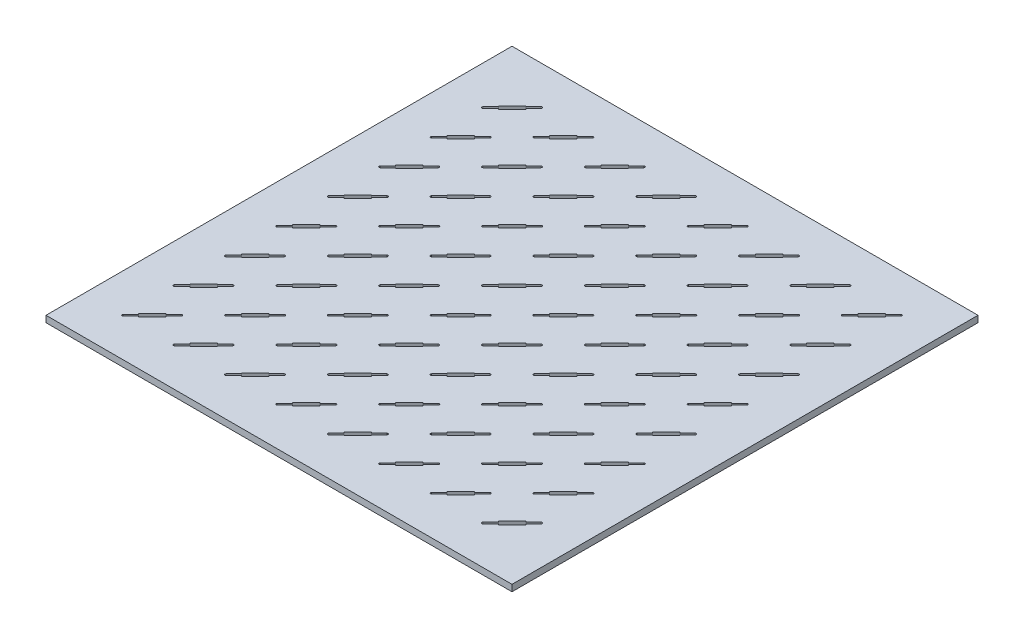
SolidWorks part; units mm, degrees
material "Acrylic (Medium-high impact)"
ref_plane "Front Plane" through (0, 0, 0) normal (0, 0, 1) x (1, 0, 0)
ref_plane "Top Plane" through (0, 0, 0) normal (0, 1, 0) x (1, 0, 0)
ref_plane "Right Plane" through (0, 0, 0) normal (1, 0, 0) x (0, 0, -1)
sketch "Sketch1" plane through (0, 0, 0) normal (0, 1, 0) x (1, 0, 0)
  line L1 (0, 0) -> (431.8, 0)
  line L2 (0, 0) -> (0, 431.8)
  line L3 (0, 431.8) -> (431.8, 431.8)
  line L4 (431.8, 0) -> (431.8, 431.8)
  dimension "D1" = 431.8
  dimension "D2" = 431.8
extrude "Boss-Extrude1" add sketch "Sketch1" along normal blind 6
sketch "Sketch2" plane through (0, 6, 0) normal (0, 1, 0) x (1, 0, 0)
  line L0 (73.025, 25.4) -> (73.025, 73.025) construction
  line L1 (25.4, 25.4) -> (73.025, 25.4) construction
  line L2 (25.4, 25.4) -> (25.4, 73.025) construction
  line L3 (25.4, 73.025) -> (73.025, 73.025) construction
  line L4 (73.025, 25.4) -> (73.025, 73.025) construction
  line L5 (73.025, 25.4) -> (120.65, 25.4) construction
  line L6 (120.65, 25.4) -> (120.65, 73.025) construction
  line L7 (73.025, 73.025) -> (120.65, 73.025) construction
  line L8 (120.65, 25.4) -> (120.65, 73.025) construction
  line L9 (120.65, 25.4) -> (168.275, 25.4) construction
  line L10 (168.275, 25.4) -> (168.275, 73.025) construction
  line L11 (120.65, 73.025) -> (168.275, 73.025) construction
  line L12 (168.275, 25.4) -> (168.275, 73.025) construction
  line L13 (168.275, 25.4) -> (215.9, 25.4) construction
  line L14 (215.9, 25.4) -> (215.9, 73.025) construction
  line L15 (168.275, 73.025) -> (215.9, 73.025) construction
  line L16 (215.9, 25.4) -> (215.9, 73.025) construction
  line L17 (215.9, 25.4) -> (263.525, 25.4) construction
  line L18 (263.525, 25.4) -> (263.525, 73.025) construction
  line L19 (215.9, 73.025) -> (263.525, 73.025) construction
  line L20 (263.525, 25.4) -> (263.525, 73.025) construction
  line L21 (263.525, 25.4) -> (311.15, 25.4) construction
  line L22 (311.15, 25.4) -> (311.15, 73.025) construction
  line L23 (263.525, 73.025) -> (311.15, 73.025) construction
  line L24 (311.15, 25.4) -> (311.15, 73.025) construction
  line L25 (311.15, 25.4) -> (358.775, 25.4) construction
  line L26 (358.775, 25.4) -> (358.775, 73.025) construction
  line L27 (311.15, 73.025) -> (358.775, 73.025) construction
  line L28 (358.775, 25.4) -> (358.775, 73.025) construction
  line L29 (358.775, 25.4) -> (406.4, 25.4) construction
  line L30 (406.4, 25.4) -> (406.4, 73.025) construction
  line L31 (358.775, 73.025) -> (406.4, 73.025) construction
  line L32 (73.025, 73.025) -> (73.025, 120.65) construction
  line L33 (73.025, 73.025) -> (120.65, 73.025) construction
  line L34 (120.65, 73.025) -> (120.65, 120.65) construction
  line L35 (73.025, 120.65) -> (120.65, 120.65) construction
  line L36 (120.65, 73.025) -> (120.65, 120.65) construction
  line L37 (120.65, 73.025) -> (168.275, 73.025) construction
  line L38 (168.275, 73.025) -> (168.275, 120.65) construction
  line L39 (120.65, 120.65) -> (168.275, 120.65) construction
  line L40 (168.275, 73.025) -> (168.275, 120.65) construction
  line L41 (168.275, 73.025) -> (215.9, 73.025) construction
  line L42 (215.9, 73.025) -> (215.9, 120.65) construction
  line L43 (168.275, 120.65) -> (215.9, 120.65) construction
  line L44 (215.9, 73.025) -> (215.9, 120.65) construction
  line L45 (215.9, 73.025) -> (263.525, 73.025) construction
  line L46 (263.525, 73.025) -> (263.525, 120.65) construction
  line L47 (215.9, 120.65) -> (263.525, 120.65) construction
  line L48 (263.525, 73.025) -> (263.525, 120.65) construction
  line L49 (263.525, 73.025) -> (311.15, 73.025) construction
  line L50 (311.15, 73.025) -> (311.15, 120.65) construction
  line L51 (263.525, 120.65) -> (311.15, 120.65) construction
  line L52 (311.15, 73.025) -> (311.15, 120.65) construction
  line L53 (311.15, 73.025) -> (358.775, 73.025) construction
  line L54 (358.775, 73.025) -> (358.775, 120.65) construction
  line L55 (311.15, 120.65) -> (358.775, 120.65) construction
  line L56 (358.775, 73.025) -> (358.775, 120.65) construction
  line L57 (358.775, 73.025) -> (406.4, 73.025) construction
  line L58 (406.4, 73.025) -> (406.4, 120.65) construction
  line L59 (358.775, 120.65) -> (406.4, 120.65) construction
  line L60 (73.025, 120.65) -> (73.025, 168.275) construction
  line L61 (73.025, 120.65) -> (120.65, 120.65) construction
  line L62 (120.65, 120.65) -> (120.65, 168.275) construction
  line L63 (73.025, 168.275) -> (120.65, 168.275) construction
  line L64 (120.65, 120.65) -> (120.65, 168.275) construction
  line L65 (120.65, 120.65) -> (168.275, 120.65) construction
  line L66 (168.275, 120.65) -> (168.275, 168.275) construction
  line L67 (120.65, 168.275) -> (168.275, 168.275) construction
  line L68 (168.275, 120.65) -> (168.275, 168.275) construction
  line L69 (168.275, 120.65) -> (215.9, 120.65) construction
  line L70 (215.9, 120.65) -> (215.9, 168.275) construction
  line L71 (168.275, 168.275) -> (215.9, 168.275) construction
  line L72 (215.9, 120.65) -> (215.9, 168.275) construction
  line L73 (215.9, 120.65) -> (263.525, 120.65) construction
  line L74 (263.525, 120.65) -> (263.525, 168.275) construction
  line L75 (215.9, 168.275) -> (263.525, 168.275) construction
  line L76 (263.525, 120.65) -> (263.525, 168.275) construction
  line L77 (263.525, 120.65) -> (311.15, 120.65) construction
  line L78 (311.15, 120.65) -> (311.15, 168.275) construction
  line L79 (263.525, 168.275) -> (311.15, 168.275) construction
  line L80 (311.15, 120.65) -> (311.15, 168.275) construction
  line L81 (311.15, 120.65) -> (358.775, 120.65) construction
  line L82 (358.775, 120.65) -> (358.775, 168.275) construction
  line L83 (311.15, 168.275) -> (358.775, 168.275) construction
  line L84 (358.775, 120.65) -> (358.775, 168.275) construction
  line L85 (358.775, 120.65) -> (406.4, 120.65) construction
  line L86 (406.4, 120.65) -> (406.4, 168.275) construction
  line L87 (358.775, 168.275) -> (406.4, 168.275) construction
  line L88 (73.025, 168.275) -> (73.025, 215.9) construction
  line L89 (73.025, 168.275) -> (120.65, 168.275) construction
  line L90 (120.65, 168.275) -> (120.65, 215.9) construction
  line L91 (73.025, 215.9) -> (120.65, 215.9) construction
  line L92 (120.65, 168.275) -> (120.65, 215.9) construction
  line L93 (120.65, 168.275) -> (168.275, 168.275) construction
  line L94 (168.275, 168.275) -> (168.275, 215.9) construction
  line L95 (120.65, 215.9) -> (168.275, 215.9) construction
  line L96 (168.275, 168.275) -> (168.275, 215.9) construction
  line L97 (168.275, 168.275) -> (215.9, 168.275) construction
  line L98 (215.9, 168.275) -> (215.9, 215.9) construction
  line L99 (168.275, 215.9) -> (215.9, 215.9) construction
  line L100 (215.9, 168.275) -> (215.9, 215.9) construction
  line L101 (215.9, 168.275) -> (263.525, 168.275) construction
  line L102 (263.525, 168.275) -> (263.525, 215.9) construction
  line L103 (215.9, 215.9) -> (263.525, 215.9) construction
  line L104 (263.525, 168.275) -> (263.525, 215.9) construction
  line L105 (263.525, 168.275) -> (311.15, 168.275) construction
  line L106 (311.15, 168.275) -> (311.15, 215.9) construction
  line L107 (263.525, 215.9) -> (311.15, 215.9) construction
  line L108 (311.15, 168.275) -> (311.15, 215.9) construction
  line L109 (311.15, 168.275) -> (358.775, 168.275) construction
  line L110 (358.775, 168.275) -> (358.775, 215.9) construction
  line L111 (311.15, 215.9) -> (358.775, 215.9) construction
  line L112 (358.775, 168.275) -> (358.775, 215.9) construction
  line L113 (358.775, 168.275) -> (406.4, 168.275) construction
  line L114 (406.4, 168.275) -> (406.4, 215.9) construction
  line L115 (358.775, 215.9) -> (406.4, 215.9) construction
  line L116 (73.025, 215.9) -> (73.025, 263.525) construction
  line L117 (73.025, 215.9) -> (120.65, 215.9) construction
  line L118 (120.65, 215.9) -> (120.65, 263.525) construction
  line L119 (73.025, 263.525) -> (120.65, 263.525) construction
  line L120 (120.65, 215.9) -> (120.65, 263.525) construction
  line L121 (120.65, 215.9) -> (168.275, 215.9) construction
  line L122 (168.275, 215.9) -> (168.275, 263.525) construction
  line L123 (120.65, 263.525) -> (168.275, 263.525) construction
  line L124 (168.275, 215.9) -> (168.275, 263.525) construction
  line L125 (168.275, 215.9) -> (215.9, 215.9) construction
  line L126 (215.9, 215.9) -> (215.9, 263.525) construction
  line L127 (168.275, 263.525) -> (215.9, 263.525) construction
  line L128 (215.9, 215.9) -> (215.9, 263.525) construction
  line L129 (215.9, 215.9) -> (263.525, 215.9) construction
  line L130 (263.525, 215.9) -> (263.525, 263.525) construction
  line L131 (215.9, 263.525) -> (263.525, 263.525) construction
  line L132 (263.525, 215.9) -> (263.525, 263.525) construction
  line L133 (263.525, 215.9) -> (311.15, 215.9) construction
  line L134 (311.15, 215.9) -> (311.15, 263.525) construction
  line L135 (263.525, 263.525) -> (311.15, 263.525) construction
  line L136 (311.15, 215.9) -> (311.15, 263.525) construction
  line L137 (311.15, 215.9) -> (358.775, 215.9) construction
  line L138 (358.775, 215.9) -> (358.775, 263.525) construction
  line L139 (311.15, 263.525) -> (358.775, 263.525) construction
  line L140 (358.775, 215.9) -> (358.775, 263.525) construction
  line L141 (358.775, 215.9) -> (406.4, 215.9) construction
  line L142 (406.4, 215.9) -> (406.4, 263.525) construction
  line L143 (358.775, 263.525) -> (406.4, 263.525) construction
  line L144 (73.025, 263.525) -> (73.025, 311.15) construction
  line L145 (73.025, 263.525) -> (120.65, 263.525) construction
  line L146 (120.65, 263.525) -> (120.65, 311.15) construction
  line L147 (73.025, 311.15) -> (120.65, 311.15) construction
  line L148 (120.65, 263.525) -> (120.65, 311.15) construction
  line L149 (120.65, 263.525) -> (168.275, 263.525) construction
  line L150 (168.275, 263.525) -> (168.275, 311.15) construction
  line L151 (120.65, 311.15) -> (168.275, 311.15) construction
  line L152 (168.275, 263.525) -> (168.275, 311.15) construction
  line L153 (168.275, 263.525) -> (215.9, 263.525) construction
  line L154 (215.9, 263.525) -> (215.9, 311.15) construction
  line L155 (168.275, 311.15) -> (215.9, 311.15) construction
  line L156 (215.9, 263.525) -> (215.9, 311.15) construction
  line L157 (215.9, 263.525) -> (263.525, 263.525) construction
  line L158 (263.525, 263.525) -> (263.525, 311.15) construction
  line L159 (215.9, 311.15) -> (263.525, 311.15) construction
  line L160 (263.525, 263.525) -> (263.525, 311.15) construction
  line L161 (263.525, 263.525) -> (311.15, 263.525) construction
  line L162 (311.15, 263.525) -> (311.15, 311.15) construction
  line L163 (263.525, 311.15) -> (311.15, 311.15) construction
  line L164 (311.15, 263.525) -> (311.15, 311.15) construction
  line L165 (311.15, 263.525) -> (358.775, 263.525) construction
  line L166 (358.775, 263.525) -> (358.775, 311.15) construction
  line L167 (311.15, 311.15) -> (358.775, 311.15) construction
  line L168 (358.775, 263.525) -> (358.775, 311.15) construction
  line L169 (358.775, 263.525) -> (406.4, 263.525) construction
  line L170 (406.4, 263.525) -> (406.4, 311.15) construction
  line L171 (358.775, 311.15) -> (406.4, 311.15) construction
  line L172 (73.025, 311.15) -> (73.025, 358.775) construction
  line L173 (73.025, 311.15) -> (120.65, 311.15) construction
  line L174 (120.65, 311.15) -> (120.65, 358.775) construction
  line L175 (73.025, 358.775) -> (120.65, 358.775) construction
  line L176 (120.65, 311.15) -> (120.65, 358.775) construction
  line L177 (120.65, 311.15) -> (168.275, 311.15) construction
  line L178 (168.275, 311.15) -> (168.275, 358.775) construction
  line L179 (120.65, 358.775) -> (168.275, 358.775) construction
  line L180 (168.275, 311.15) -> (168.275, 358.775) construction
  line L181 (168.275, 311.15) -> (215.9, 311.15) construction
  line L182 (215.9, 311.15) -> (215.9, 358.775) construction
  line L183 (168.275, 358.775) -> (215.9, 358.775) construction
  line L184 (215.9, 311.15) -> (215.9, 358.775) construction
  line L185 (215.9, 311.15) -> (263.525, 311.15) construction
  line L186 (263.525, 311.15) -> (263.525, 358.775) construction
  line L187 (215.9, 358.775) -> (263.525, 358.775) construction
  line L188 (263.525, 311.15) -> (263.525, 358.775) construction
  line L189 (263.525, 311.15) -> (311.15, 311.15) construction
  line L190 (311.15, 311.15) -> (311.15, 358.775) construction
  line L191 (263.525, 358.775) -> (311.15, 358.775) construction
  line L192 (311.15, 311.15) -> (311.15, 358.775) construction
  line L193 (311.15, 311.15) -> (358.775, 311.15) construction
  line L194 (358.775, 311.15) -> (358.775, 358.775) construction
  line L195 (311.15, 358.775) -> (358.775, 358.775) construction
  line L196 (358.775, 311.15) -> (358.775, 358.775) construction
  line L197 (358.775, 311.15) -> (406.4, 311.15) construction
  line L198 (406.4, 311.15) -> (406.4, 358.775) construction
  line L199 (358.775, 358.775) -> (406.4, 358.775) construction
  line L200 (73.025, 358.775) -> (73.025, 406.4) construction
  line L201 (73.025, 358.775) -> (120.65, 358.775) construction
  line L202 (120.65, 358.775) -> (120.65, 406.4) construction
  line L203 (73.025, 406.4) -> (120.65, 406.4) construction
  line L204 (120.65, 358.775) -> (120.65, 406.4) construction
  line L205 (120.65, 358.775) -> (168.275, 358.775) construction
  line L206 (168.275, 358.775) -> (168.275, 406.4) construction
  line L207 (120.65, 406.4) -> (168.275, 406.4) construction
  line L208 (168.275, 358.775) -> (168.275, 406.4) construction
  line L209 (168.275, 358.775) -> (215.9, 358.775) construction
  line L210 (215.9, 358.775) -> (215.9, 406.4) construction
  line L211 (168.275, 406.4) -> (215.9, 406.4) construction
  line L212 (215.9, 358.775) -> (215.9, 406.4) construction
  line L213 (215.9, 358.775) -> (263.525, 358.775) construction
  line L214 (263.525, 358.775) -> (263.525, 406.4) construction
  line L215 (215.9, 406.4) -> (263.525, 406.4) construction
  line L216 (263.525, 358.775) -> (263.525, 406.4) construction
  line L217 (263.525, 358.775) -> (311.15, 358.775) construction
  line L218 (311.15, 358.775) -> (311.15, 406.4) construction
  line L219 (263.525, 406.4) -> (311.15, 406.4) construction
  line L220 (311.15, 358.775) -> (311.15, 406.4) construction
  line L221 (311.15, 358.775) -> (358.775, 358.775) construction
  line L222 (358.775, 358.775) -> (358.775, 406.4) construction
  line L223 (311.15, 406.4) -> (358.775, 406.4) construction
  line L224 (358.775, 358.775) -> (358.775, 406.4) construction
  line L225 (358.775, 358.775) -> (406.4, 358.775) construction
  line L226 (406.4, 358.775) -> (406.4, 406.4) construction
  line L227 (358.775, 406.4) -> (406.4, 406.4) construction
  line L228 (25.4, 73.025) -> (25.4, 120.65) construction
  line L229 (25.4, 73.025) -> (73.025, 73.025) construction
  line L230 (73.025, 73.025) -> (73.025, 120.65) construction
  line L231 (25.4, 120.65) -> (73.025, 120.65) construction
  line L232 (25.4, 120.65) -> (25.4, 168.275) construction
  line L233 (25.4, 120.65) -> (73.025, 120.65) construction
  line L234 (73.025, 120.65) -> (73.025, 168.275) construction
  line L235 (25.4, 168.275) -> (73.025, 168.275) construction
  line L236 (25.4, 168.275) -> (25.4, 215.9) construction
  line L237 (25.4, 168.275) -> (73.025, 168.275) construction
  line L238 (73.025, 168.275) -> (73.025, 215.9) construction
  line L239 (25.4, 215.9) -> (73.025, 215.9) construction
  line L240 (25.4, 215.9) -> (25.4, 263.525) construction
  line L241 (25.4, 215.9) -> (73.025, 215.9) construction
  line L242 (73.025, 215.9) -> (73.025, 263.525) construction
  line L243 (25.4, 263.525) -> (73.025, 263.525) construction
  line L244 (25.4, 263.525) -> (25.4, 311.15) construction
  line L245 (25.4, 263.525) -> (73.025, 263.525) construction
  line L246 (73.025, 263.525) -> (73.025, 311.15) construction
  line L247 (25.4, 311.15) -> (73.025, 311.15) construction
  line L248 (25.4, 311.15) -> (25.4, 358.775) construction
  line L249 (25.4, 311.15) -> (73.025, 311.15) construction
  line L250 (73.025, 311.15) -> (73.025, 358.775) construction
  line L251 (25.4, 358.775) -> (73.025, 358.775) construction
  line L252 (25.4, 358.775) -> (25.4, 406.4) construction
  line L253 (25.4, 358.775) -> (73.025, 358.775) construction
  line L254 (73.025, 358.775) -> (73.025, 406.4) construction
  line L255 (25.4, 406.4) -> (73.025, 406.4) construction
  line L256 (0, 0) -> (431.8, 0) construction
  line L257 (0, 431.8) -> (0, 0) construction
  line L259 (431.8, 431.8) -> (0, 431.8) construction
  line L260 (431.8, 0) -> (431.8, 431.8) construction
  line L261 (73.025, 73.025) -> (25.4, 25.4) construction
  line L266 (42.1408, 43.555) -> (35.0697, 36.4839)
  line L906 (56.99, 54.1616) -> (56.2829, 54.8687)
  line L922 (56.99, 54.1616) -> (44.2621, 41.4336)
  line L923 (44.2621, 41.4336) -> (43.555, 42.1408)
  line L924 (54.1616, 56.99) -> (41.4336, 44.2621)
  line L925 (35.0697, 36.4839) -> (36.4839, 35.0697)
  line L926 (36.4839, 35.0697) -> (43.555, 42.1408)
  line L927 (42.1408, 43.555) -> (41.4336, 44.2621)
  line L928 (54.8687, 56.2829) -> (61.9397, 63.354)
  line L929 (61.9397, 63.354) -> (63.354, 61.9397)
  line L930 (63.354, 61.9397) -> (56.2829, 54.8687)
  line L931 (54.8687, 56.2829) -> (54.1616, 56.99)
  line L932 (25.4, 73.025) -> (73.025, 25.4) construction
  line L933 (56.99, 101.7916) -> (56.2829, 102.4987)
  line L934 (63.354, 109.5697) -> (56.2829, 102.4987)
  line L935 (61.9397, 110.984) -> (63.354, 109.5697)
  line L936 (54.8687, 103.9129) -> (61.9397, 110.984)
  line L937 (54.8687, 103.9129) -> (54.1616, 104.62)
  line L938 (54.1616, 104.62) -> (41.4336, 91.8921)
  line L939 (42.1408, 91.185) -> (41.4336, 91.8921)
  line L940 (42.1408, 91.185) -> (35.0697, 84.1139)
  line L941 (35.0697, 84.1139) -> (36.4839, 82.6997)
  line L942 (36.4839, 82.6997) -> (43.555, 89.7708)
  line L943 (44.2621, 89.0636) -> (43.555, 89.7708)
  line L944 (56.99, 101.7916) -> (44.2621, 89.0636)
  line L945 (56.99, 149.4216) -> (56.2829, 150.1287)
  line L946 (63.354, 157.1997) -> (56.2829, 150.1287)
  line L947 (61.9397, 158.614) -> (63.354, 157.1997)
  line L948 (54.8687, 151.5429) -> (61.9397, 158.614)
  line L949 (54.8687, 151.5429) -> (54.1616, 152.25)
  line L950 (54.1616, 152.25) -> (41.4336, 139.5221)
  line L951 (42.1408, 138.815) -> (41.4336, 139.5221)
  line L952 (42.1408, 138.815) -> (35.0697, 131.7439)
  line L953 (35.0697, 131.7439) -> (36.4839, 130.3297)
  line L954 (36.4839, 130.3297) -> (43.555, 137.4008)
  line L955 (44.2621, 136.6936) -> (43.555, 137.4008)
  line L956 (56.99, 149.4216) -> (44.2621, 136.6936)
  line L957 (56.99, 197.0516) -> (56.2829, 197.7587)
  line L958 (63.354, 204.8297) -> (56.2829, 197.7587)
  line L959 (61.9397, 206.244) -> (63.354, 204.8297)
  line L960 (54.8687, 199.1729) -> (61.9397, 206.244)
  line L961 (54.8687, 199.1729) -> (54.1616, 199.88)
  line L962 (54.1616, 199.88) -> (41.4336, 187.1521)
  line L963 (42.1408, 186.445) -> (41.4336, 187.1521)
  line L964 (42.1408, 186.445) -> (35.0697, 179.3739)
  line L965 (35.0697, 179.3739) -> (36.4839, 177.9597)
  line L966 (36.4839, 177.9597) -> (43.555, 185.0308)
  line L967 (44.2621, 184.3236) -> (43.555, 185.0308)
  line L968 (56.99, 197.0516) -> (44.2621, 184.3236)
  line L969 (56.99, 244.6816) -> (56.2829, 245.3887)
  line L970 (63.354, 252.4597) -> (56.2829, 245.3887)
  line L971 (61.9397, 253.874) -> (63.354, 252.4597)
  line L972 (54.8687, 246.8029) -> (61.9397, 253.874)
  line L973 (54.8687, 246.8029) -> (54.1616, 247.51)
  line L974 (54.1616, 247.51) -> (41.4336, 234.7821)
  line L975 (42.1408, 234.075) -> (41.4336, 234.7821)
  line L976 (42.1408, 234.075) -> (35.0697, 227.0039)
  line L977 (35.0697, 227.0039) -> (36.4839, 225.5897)
  line L978 (36.4839, 225.5897) -> (43.555, 232.6608)
  line L979 (44.2621, 231.9536) -> (43.555, 232.6608)
  line L980 (56.99, 244.6816) -> (44.2621, 231.9536)
  line L981 (56.99, 292.3116) -> (56.2829, 293.0187)
  line L982 (63.354, 300.0897) -> (56.2829, 293.0187)
  line L983 (61.9397, 301.504) -> (63.354, 300.0897)
  line L984 (54.8687, 294.4329) -> (61.9397, 301.504)
  line L985 (54.8687, 294.4329) -> (54.1616, 295.14)
  line L986 (54.1616, 295.14) -> (41.4336, 282.4121)
  line L987 (42.1408, 281.705) -> (41.4336, 282.4121)
  line L988 (42.1408, 281.705) -> (35.0697, 274.6339)
  line L989 (35.0697, 274.6339) -> (36.4839, 273.2197)
  line L990 (36.4839, 273.2197) -> (43.555, 280.2908)
  line L991 (44.2621, 279.5836) -> (43.555, 280.2908)
  line L992 (56.99, 292.3116) -> (44.2621, 279.5836)
  line L993 (56.99, 339.9416) -> (56.2829, 340.6487)
  line L994 (63.354, 347.7197) -> (56.2829, 340.6487)
  line L995 (61.9397, 349.134) -> (63.354, 347.7197)
  line L996 (54.8687, 342.0629) -> (61.9397, 349.134)
  line L997 (54.8687, 342.0629) -> (54.1616, 342.77)
  line L998 (54.1616, 342.77) -> (41.4336, 330.0421)
  line L999 (42.1408, 329.335) -> (41.4336, 330.0421)
  line L1000 (42.1408, 329.335) -> (35.0697, 322.2639)
  line L1001 (35.0697, 322.2639) -> (36.4839, 320.8497)
  line L1002 (36.4839, 320.8497) -> (43.555, 327.9208)
  line L1003 (44.2621, 327.2136) -> (43.555, 327.9208)
  line L1004 (56.99, 339.9416) -> (44.2621, 327.2136)
  line L1005 (56.99, 387.5716) -> (56.2829, 388.2787)
  line L1006 (63.354, 395.3497) -> (56.2829, 388.2787)
  line L1007 (61.9397, 396.764) -> (63.354, 395.3497)
  line L1008 (54.8687, 389.6929) -> (61.9397, 396.764)
  line L1009 (54.8687, 389.6929) -> (54.1616, 390.4)
  line L1010 (54.1616, 390.4) -> (41.4336, 377.6721)
  line L1011 (42.1408, 376.965) -> (41.4336, 377.6721)
  line L1012 (42.1408, 376.965) -> (35.0697, 369.8939)
  line L1013 (35.0697, 369.8939) -> (36.4839, 368.4797)
  line L1014 (36.4839, 368.4797) -> (43.555, 375.5508)
  line L1015 (44.2621, 374.8436) -> (43.555, 375.5508)
  line L1016 (56.99, 387.5716) -> (44.2621, 374.8436)
  line L1017 (104.62, 101.7916) -> (103.9129, 102.4987)
  line L1018 (110.984, 109.5697) -> (103.9129, 102.4987)
  line L1019 (109.5697, 110.984) -> (110.984, 109.5697)
  line L1020 (102.4987, 103.9129) -> (109.5697, 110.984)
  line L1021 (102.4987, 103.9129) -> (101.7916, 104.62)
  line L1022 (101.7916, 104.62) -> (89.0636, 91.8921)
  line L1023 (89.7708, 91.185) -> (89.0636, 91.8921)
  line L1024 (89.7708, 91.185) -> (82.6997, 84.1139)
  line L1025 (82.6997, 84.1139) -> (84.1139, 82.6997)
  line L1026 (84.1139, 82.6997) -> (91.185, 89.7708)
  line L1027 (91.8921, 89.0636) -> (91.185, 89.7708)
  line L1028 (104.62, 101.7916) -> (91.8921, 89.0636)
  line L1029 (104.62, 149.4216) -> (103.9129, 150.1287)
  line L1030 (110.984, 157.1997) -> (103.9129, 150.1287)
  line L1031 (109.5697, 158.614) -> (110.984, 157.1997)
  line L1032 (102.4987, 151.5429) -> (109.5697, 158.614)
  line L1033 (102.4987, 151.5429) -> (101.7916, 152.25)
  line L1034 (101.7916, 152.25) -> (89.0636, 139.5221)
  line L1035 (89.7708, 138.815) -> (89.0636, 139.5221)
  line L1036 (89.7708, 138.815) -> (82.6997, 131.7439)
  line L1037 (82.6997, 131.7439) -> (84.1139, 130.3297)
  line L1038 (84.1139, 130.3297) -> (91.185, 137.4008)
  line L1039 (91.8921, 136.6936) -> (91.185, 137.4008)
  line L1040 (104.62, 149.4216) -> (91.8921, 136.6936)
  line L1041 (104.62, 197.0516) -> (103.9129, 197.7587)
  line L1042 (110.984, 204.8297) -> (103.9129, 197.7587)
  line L1043 (109.5697, 206.244) -> (110.984, 204.8297)
  line L1044 (102.4987, 199.1729) -> (109.5697, 206.244)
  line L1045 (102.4987, 199.1729) -> (101.7916, 199.88)
  line L1046 (101.7916, 199.88) -> (89.0636, 187.1521)
  line L1047 (89.7708, 186.445) -> (89.0636, 187.1521)
  line L1048 (89.7708, 186.445) -> (82.6997, 179.3739)
  line L1049 (82.6997, 179.3739) -> (84.1139, 177.9597)
  line L1050 (84.1139, 177.9597) -> (91.185, 185.0308)
  line L1051 (91.8921, 184.3236) -> (91.185, 185.0308)
  line L1052 (104.62, 197.0516) -> (91.8921, 184.3236)
  line L1053 (104.62, 244.6816) -> (103.9129, 245.3887)
  line L1054 (110.984, 252.4597) -> (103.9129, 245.3887)
  line L1055 (109.5697, 253.874) -> (110.984, 252.4597)
  line L1056 (102.4987, 246.8029) -> (109.5697, 253.874)
  line L1057 (102.4987, 246.8029) -> (101.7916, 247.51)
  line L1058 (101.7916, 247.51) -> (89.0636, 234.7821)
  line L1059 (89.7708, 234.075) -> (89.0636, 234.7821)
  line L1060 (89.7708, 234.075) -> (82.6997, 227.0039)
  line L1061 (82.6997, 227.0039) -> (84.1139, 225.5897)
  line L1062 (84.1139, 225.5897) -> (91.185, 232.6608)
  line L1063 (91.8921, 231.9536) -> (91.185, 232.6608)
  line L1064 (104.62, 244.6816) -> (91.8921, 231.9536)
  line L1065 (104.62, 292.3116) -> (103.9129, 293.0187)
  line L1066 (110.984, 300.0897) -> (103.9129, 293.0187)
  line L1067 (109.5697, 301.504) -> (110.984, 300.0897)
  line L1068 (102.4987, 294.4329) -> (109.5697, 301.504)
  line L1069 (102.4987, 294.4329) -> (101.7916, 295.14)
  line L1070 (101.7916, 295.14) -> (89.0636, 282.4121)
  line L1071 (89.7708, 281.705) -> (89.0636, 282.4121)
  line L1072 (89.7708, 281.705) -> (82.6997, 274.6339)
  line L1073 (82.6997, 274.6339) -> (84.1139, 273.2197)
  line L1074 (84.1139, 273.2197) -> (91.185, 280.2908)
  line L1075 (91.8921, 279.5836) -> (91.185, 280.2908)
  line L1076 (104.62, 292.3116) -> (91.8921, 279.5836)
  line L1077 (104.62, 339.9416) -> (103.9129, 340.6487)
  line L1078 (110.984, 347.7197) -> (103.9129, 340.6487)
  line L1079 (109.5697, 349.134) -> (110.984, 347.7197)
  line L1080 (102.4987, 342.0629) -> (109.5697, 349.134)
  line L1081 (102.4987, 342.0629) -> (101.7916, 342.77)
  line L1082 (101.7916, 342.77) -> (89.0636, 330.0421)
  line L1083 (89.7708, 329.335) -> (89.0636, 330.0421)
  line L1084 (89.7708, 329.335) -> (82.6997, 322.2639)
  line L1085 (82.6997, 322.2639) -> (84.1139, 320.8497)
  line L1086 (84.1139, 320.8497) -> (91.185, 327.9208)
  line L1087 (91.8921, 327.2136) -> (91.185, 327.9208)
  line L1088 (104.62, 339.9416) -> (91.8921, 327.2136)
  line L1089 (104.62, 387.5716) -> (103.9129, 388.2787)
  line L1090 (110.984, 395.3497) -> (103.9129, 388.2787)
  line L1091 (109.5697, 396.764) -> (110.984, 395.3497)
  line L1092 (102.4987, 389.6929) -> (109.5697, 396.764)
  line L1093 (102.4987, 389.6929) -> (101.7916, 390.4)
  line L1094 (101.7916, 390.4) -> (89.0636, 377.6721)
  line L1095 (89.7708, 376.965) -> (89.0636, 377.6721)
  line L1096 (89.7708, 376.965) -> (82.6997, 369.8939)
  line L1097 (82.6997, 369.8939) -> (84.1139, 368.4797)
  line L1098 (84.1139, 368.4797) -> (91.185, 375.5508)
  line L1099 (91.8921, 374.8436) -> (91.185, 375.5508)
  line L1100 (104.62, 387.5716) -> (91.8921, 374.8436)
  line L1101 (152.25, 101.7916) -> (151.5429, 102.4987)
  line L1102 (158.614, 109.5697) -> (151.5429, 102.4987)
  line L1103 (157.1997, 110.984) -> (158.614, 109.5697)
  line L1104 (150.1287, 103.9129) -> (157.1997, 110.984)
  line L1105 (150.1287, 103.9129) -> (149.4216, 104.62)
  line L1106 (149.4216, 104.62) -> (136.6936, 91.8921)
  line L1107 (137.4008, 91.185) -> (136.6936, 91.8921)
  line L1108 (137.4008, 91.185) -> (130.3297, 84.1139)
  line L1109 (130.3297, 84.1139) -> (131.7439, 82.6997)
  line L1110 (131.7439, 82.6997) -> (138.815, 89.7708)
  line L1111 (139.5221, 89.0636) -> (138.815, 89.7708)
  line L1112 (152.25, 101.7916) -> (139.5221, 89.0636)
  line L1113 (152.25, 149.4216) -> (151.5429, 150.1287)
  line L1114 (158.614, 157.1997) -> (151.5429, 150.1287)
  line L1115 (157.1997, 158.614) -> (158.614, 157.1997)
  line L1116 (150.1287, 151.5429) -> (157.1997, 158.614)
  line L1117 (150.1287, 151.5429) -> (149.4216, 152.25)
  line L1118 (149.4216, 152.25) -> (136.6936, 139.5221)
  line L1119 (137.4008, 138.815) -> (136.6936, 139.5221)
  line L1120 (137.4008, 138.815) -> (130.3297, 131.7439)
  line L1121 (130.3297, 131.7439) -> (131.7439, 130.3297)
  line L1122 (131.7439, 130.3297) -> (138.815, 137.4008)
  line L1123 (139.5221, 136.6936) -> (138.815, 137.4008)
  line L1124 (152.25, 149.4216) -> (139.5221, 136.6936)
  line L1125 (152.25, 197.0516) -> (151.5429, 197.7587)
  line L1126 (158.614, 204.8297) -> (151.5429, 197.7587)
  line L1127 (157.1997, 206.244) -> (158.614, 204.8297)
  line L1128 (150.1287, 199.1729) -> (157.1997, 206.244)
  line L1129 (150.1287, 199.1729) -> (149.4216, 199.88)
  line L1130 (149.4216, 199.88) -> (136.6936, 187.1521)
  line L1131 (137.4008, 186.445) -> (136.6936, 187.1521)
  line L1132 (137.4008, 186.445) -> (130.3297, 179.3739)
  line L1133 (130.3297, 179.3739) -> (131.7439, 177.9597)
  line L1134 (131.7439, 177.9597) -> (138.815, 185.0308)
  line L1135 (139.5221, 184.3236) -> (138.815, 185.0308)
  line L1136 (152.25, 197.0516) -> (139.5221, 184.3236)
  line L1137 (152.25, 244.6816) -> (151.5429, 245.3887)
  line L1138 (158.614, 252.4597) -> (151.5429, 245.3887)
  line L1139 (157.1997, 253.874) -> (158.614, 252.4597)
  line L1140 (150.1287, 246.8029) -> (157.1997, 253.874)
  line L1141 (150.1287, 246.8029) -> (149.4216, 247.51)
  line L1142 (149.4216, 247.51) -> (136.6936, 234.7821)
  line L1143 (137.4008, 234.075) -> (136.6936, 234.7821)
  line L1144 (137.4008, 234.075) -> (130.3297, 227.0039)
  line L1145 (130.3297, 227.0039) -> (131.7439, 225.5897)
  line L1146 (131.7439, 225.5897) -> (138.815, 232.6608)
  line L1147 (139.5221, 231.9536) -> (138.815, 232.6608)
  line L1148 (152.25, 244.6816) -> (139.5221, 231.9536)
  line L1149 (152.25, 292.3116) -> (151.5429, 293.0187)
  line L1150 (158.614, 300.0897) -> (151.5429, 293.0187)
  line L1151 (157.1997, 301.504) -> (158.614, 300.0897)
  line L1152 (150.1287, 294.4329) -> (157.1997, 301.504)
  line L1153 (150.1287, 294.4329) -> (149.4216, 295.14)
  line L1154 (149.4216, 295.14) -> (136.6936, 282.4121)
  line L1155 (137.4008, 281.705) -> (136.6936, 282.4121)
  line L1156 (137.4008, 281.705) -> (130.3297, 274.6339)
  line L1157 (130.3297, 274.6339) -> (131.7439, 273.2197)
  line L1158 (131.7439, 273.2197) -> (138.815, 280.2908)
  line L1159 (139.5221, 279.5836) -> (138.815, 280.2908)
  line L1160 (152.25, 292.3116) -> (139.5221, 279.5836)
  line L1161 (152.25, 339.9416) -> (151.5429, 340.6487)
  line L1162 (158.614, 347.7197) -> (151.5429, 340.6487)
  line L1163 (157.1997, 349.134) -> (158.614, 347.7197)
  line L1164 (150.1287, 342.0629) -> (157.1997, 349.134)
  line L1165 (150.1287, 342.0629) -> (149.4216, 342.77)
  line L1166 (149.4216, 342.77) -> (136.6936, 330.0421)
  line L1167 (137.4008, 329.335) -> (136.6936, 330.0421)
  line L1168 (137.4008, 329.335) -> (130.3297, 322.2639)
  line L1169 (130.3297, 322.2639) -> (131.7439, 320.8497)
  line L1170 (131.7439, 320.8497) -> (138.815, 327.9208)
  line L1171 (139.5221, 327.2136) -> (138.815, 327.9208)
  line L1172 (152.25, 339.9416) -> (139.5221, 327.2136)
  line L1173 (152.25, 387.5716) -> (151.5429, 388.2787)
  line L1174 (158.614, 395.3497) -> (151.5429, 388.2787)
  line L1175 (157.1997, 396.764) -> (158.614, 395.3497)
  line L1176 (150.1287, 389.6929) -> (157.1997, 396.764)
  line L1177 (150.1287, 389.6929) -> (149.4216, 390.4)
  line L1178 (149.4216, 390.4) -> (136.6936, 377.6721)
  line L1179 (137.4008, 376.965) -> (136.6936, 377.6721)
  line L1180 (137.4008, 376.965) -> (130.3297, 369.8939)
  line L1181 (130.3297, 369.8939) -> (131.7439, 368.4797)
  line L1182 (131.7439, 368.4797) -> (138.815, 375.5508)
  line L1183 (139.5221, 374.8436) -> (138.815, 375.5508)
  line L1184 (152.25, 387.5716) -> (139.5221, 374.8436)
  line L1185 (199.88, 101.7916) -> (199.1729, 102.4987)
  line L1186 (206.244, 109.5697) -> (199.1729, 102.4987)
  line L1187 (204.8297, 110.984) -> (206.244, 109.5697)
  line L1188 (197.7587, 103.9129) -> (204.8297, 110.984)
  line L1189 (197.7587, 103.9129) -> (197.0516, 104.62)
  line L1190 (197.0516, 104.62) -> (184.3236, 91.8921)
  line L1191 (185.0308, 91.185) -> (184.3236, 91.8921)
  line L1192 (185.0308, 91.185) -> (177.9597, 84.1139)
  line L1193 (177.9597, 84.1139) -> (179.3739, 82.6997)
  line L1194 (179.3739, 82.6997) -> (186.445, 89.7708)
  line L1195 (187.1521, 89.0636) -> (186.445, 89.7708)
  line L1196 (199.88, 101.7916) -> (187.1521, 89.0636)
  line L1197 (199.88, 149.4216) -> (199.1729, 150.1287)
  line L1198 (206.244, 157.1997) -> (199.1729, 150.1287)
  line L1199 (204.8297, 158.614) -> (206.244, 157.1997)
  line L1200 (197.7587, 151.5429) -> (204.8297, 158.614)
  line L1201 (197.7587, 151.5429) -> (197.0516, 152.25)
  line L1202 (197.0516, 152.25) -> (184.3236, 139.5221)
  line L1203 (185.0308, 138.815) -> (184.3236, 139.5221)
  line L1204 (185.0308, 138.815) -> (177.9597, 131.7439)
  line L1205 (177.9597, 131.7439) -> (179.3739, 130.3297)
  line L1206 (179.3739, 130.3297) -> (186.445, 137.4008)
  line L1207 (187.1521, 136.6936) -> (186.445, 137.4008)
  line L1208 (199.88, 149.4216) -> (187.1521, 136.6936)
  line L1209 (199.88, 197.0516) -> (199.1729, 197.7587)
  line L1210 (206.244, 204.8297) -> (199.1729, 197.7587)
  line L1211 (204.8297, 206.244) -> (206.244, 204.8297)
  line L1212 (197.7587, 199.1729) -> (204.8297, 206.244)
  line L1213 (197.7587, 199.1729) -> (197.0516, 199.88)
  line L1214 (197.0516, 199.88) -> (184.3236, 187.1521)
  line L1215 (185.0308, 186.445) -> (184.3236, 187.1521)
  line L1216 (185.0308, 186.445) -> (177.9597, 179.3739)
  line L1217 (177.9597, 179.3739) -> (179.3739, 177.9597)
  line L1218 (179.3739, 177.9597) -> (186.445, 185.0308)
  line L1219 (187.1521, 184.3236) -> (186.445, 185.0308)
  line L1220 (199.88, 197.0516) -> (187.1521, 184.3236)
  line L1221 (199.88, 244.6816) -> (199.1729, 245.3887)
  line L1222 (206.244, 252.4597) -> (199.1729, 245.3887)
  line L1223 (204.8297, 253.874) -> (206.244, 252.4597)
  line L1224 (197.7587, 246.8029) -> (204.8297, 253.874)
  line L1225 (197.7587, 246.8029) -> (197.0516, 247.51)
  line L1226 (197.0516, 247.51) -> (184.3236, 234.7821)
  line L1227 (185.0308, 234.075) -> (184.3236, 234.7821)
  line L1228 (185.0308, 234.075) -> (177.9597, 227.0039)
  line L1229 (177.9597, 227.0039) -> (179.3739, 225.5897)
  line L1230 (179.3739, 225.5897) -> (186.445, 232.6608)
  line L1231 (187.1521, 231.9536) -> (186.445, 232.6608)
  line L1232 (199.88, 244.6816) -> (187.1521, 231.9536)
  line L1233 (199.88, 292.3116) -> (199.1729, 293.0187)
  line L1234 (206.244, 300.0897) -> (199.1729, 293.0187)
  line L1235 (204.8297, 301.504) -> (206.244, 300.0897)
  line L1236 (197.7587, 294.4329) -> (204.8297, 301.504)
  line L1237 (197.7587, 294.4329) -> (197.0516, 295.14)
  line L1238 (197.0516, 295.14) -> (184.3236, 282.4121)
  line L1239 (185.0308, 281.705) -> (184.3236, 282.4121)
  line L1240 (185.0308, 281.705) -> (177.9597, 274.6339)
  line L1241 (177.9597, 274.6339) -> (179.3739, 273.2197)
  line L1242 (179.3739, 273.2197) -> (186.445, 280.2908)
  line L1243 (187.1521, 279.5836) -> (186.445, 280.2908)
  line L1244 (199.88, 292.3116) -> (187.1521, 279.5836)
  line L1245 (199.88, 339.9416) -> (199.1729, 340.6487)
  line L1246 (206.244, 347.7197) -> (199.1729, 340.6487)
  line L1247 (204.8297, 349.134) -> (206.244, 347.7197)
  line L1248 (197.7587, 342.0629) -> (204.8297, 349.134)
  line L1249 (197.7587, 342.0629) -> (197.0516, 342.77)
  line L1250 (197.0516, 342.77) -> (184.3236, 330.0421)
  line L1251 (185.0308, 329.335) -> (184.3236, 330.0421)
  line L1252 (185.0308, 329.335) -> (177.9597, 322.2639)
  line L1253 (177.9597, 322.2639) -> (179.3739, 320.8497)
  line L1254 (179.3739, 320.8497) -> (186.445, 327.9208)
  line L1255 (187.1521, 327.2136) -> (186.445, 327.9208)
  line L1256 (199.88, 339.9416) -> (187.1521, 327.2136)
  line L1257 (199.88, 387.5716) -> (199.1729, 388.2787)
  line L1258 (206.244, 395.3497) -> (199.1729, 388.2787)
  line L1259 (204.8297, 396.764) -> (206.244, 395.3497)
  line L1260 (197.7587, 389.6929) -> (204.8297, 396.764)
  line L1261 (197.7587, 389.6929) -> (197.0516, 390.4)
  line L1262 (197.0516, 390.4) -> (184.3236, 377.6721)
  line L1263 (185.0308, 376.965) -> (184.3236, 377.6721)
  line L1264 (185.0308, 376.965) -> (177.9597, 369.8939)
  line L1265 (177.9597, 369.8939) -> (179.3739, 368.4797)
  line L1266 (179.3739, 368.4797) -> (186.445, 375.5508)
  line L1267 (187.1521, 374.8436) -> (186.445, 375.5508)
  line L1268 (199.88, 387.5716) -> (187.1521, 374.8436)
  line L1269 (247.51, 101.7916) -> (246.8029, 102.4987)
  line L1270 (253.874, 109.5697) -> (246.8029, 102.4987)
  line L1271 (252.4597, 110.984) -> (253.874, 109.5697)
  line L1272 (245.3887, 103.9129) -> (252.4597, 110.984)
  line L1273 (245.3887, 103.9129) -> (244.6816, 104.62)
  line L1274 (244.6816, 104.62) -> (231.9536, 91.8921)
  line L1275 (232.6608, 91.185) -> (231.9536, 91.8921)
  line L1276 (232.6608, 91.185) -> (225.5897, 84.1139)
  line L1277 (225.5897, 84.1139) -> (227.0039, 82.6997)
  line L1278 (227.0039, 82.6997) -> (234.075, 89.7708)
  line L1279 (234.7821, 89.0636) -> (234.075, 89.7708)
  line L1280 (247.51, 101.7916) -> (234.7821, 89.0636)
  line L1281 (247.51, 149.4216) -> (246.8029, 150.1287)
  line L1282 (253.874, 157.1997) -> (246.8029, 150.1287)
  line L1283 (252.4597, 158.614) -> (253.874, 157.1997)
  line L1284 (245.3887, 151.5429) -> (252.4597, 158.614)
  line L1285 (245.3887, 151.5429) -> (244.6816, 152.25)
  line L1286 (244.6816, 152.25) -> (231.9536, 139.5221)
  line L1287 (232.6608, 138.815) -> (231.9536, 139.5221)
  line L1288 (232.6608, 138.815) -> (225.5897, 131.7439)
  line L1289 (225.5897, 131.7439) -> (227.0039, 130.3297)
  line L1290 (227.0039, 130.3297) -> (234.075, 137.4008)
  line L1291 (234.7821, 136.6936) -> (234.075, 137.4008)
  line L1292 (247.51, 149.4216) -> (234.7821, 136.6936)
  line L1293 (247.51, 197.0516) -> (246.8029, 197.7587)
  line L1294 (253.874, 204.8297) -> (246.8029, 197.7587)
  line L1295 (252.4597, 206.244) -> (253.874, 204.8297)
  line L1296 (245.3887, 199.1729) -> (252.4597, 206.244)
  line L1297 (245.3887, 199.1729) -> (244.6816, 199.88)
  line L1298 (244.6816, 199.88) -> (231.9536, 187.1521)
  line L1299 (232.6608, 186.445) -> (231.9536, 187.1521)
  line L1300 (232.6608, 186.445) -> (225.5897, 179.3739)
  line L1301 (225.5897, 179.3739) -> (227.0039, 177.9597)
  line L1302 (227.0039, 177.9597) -> (234.075, 185.0308)
  line L1303 (234.7821, 184.3236) -> (234.075, 185.0308)
  line L1304 (247.51, 197.0516) -> (234.7821, 184.3236)
  line L1305 (247.51, 244.6816) -> (246.8029, 245.3887)
  line L1306 (253.874, 252.4597) -> (246.8029, 245.3887)
  line L1307 (252.4597, 253.874) -> (253.874, 252.4597)
  line L1308 (245.3887, 246.8029) -> (252.4597, 253.874)
  line L1309 (245.3887, 246.8029) -> (244.6816, 247.51)
  line L1310 (244.6816, 247.51) -> (231.9536, 234.7821)
  line L1311 (232.6608, 234.075) -> (231.9536, 234.7821)
  line L1312 (232.6608, 234.075) -> (225.5897, 227.0039)
  line L1313 (225.5897, 227.0039) -> (227.0039, 225.5897)
  line L1314 (227.0039, 225.5897) -> (234.075, 232.6608)
  line L1315 (234.7821, 231.9536) -> (234.075, 232.6608)
  line L1316 (247.51, 244.6816) -> (234.7821, 231.9536)
  line L1317 (247.51, 292.3116) -> (246.8029, 293.0187)
  line L1318 (253.874, 300.0897) -> (246.8029, 293.0187)
  line L1319 (252.4597, 301.504) -> (253.874, 300.0897)
  line L1320 (245.3887, 294.4329) -> (252.4597, 301.504)
  line L1321 (245.3887, 294.4329) -> (244.6816, 295.14)
  line L1322 (244.6816, 295.14) -> (231.9536, 282.4121)
  line L1323 (232.6608, 281.705) -> (231.9536, 282.4121)
  line L1324 (232.6608, 281.705) -> (225.5897, 274.6339)
  line L1325 (225.5897, 274.6339) -> (227.0039, 273.2197)
  line L1326 (227.0039, 273.2197) -> (234.075, 280.2908)
  line L1327 (234.7821, 279.5836) -> (234.075, 280.2908)
  line L1328 (247.51, 292.3116) -> (234.7821, 279.5836)
  line L1329 (247.51, 339.9416) -> (246.8029, 340.6487)
  line L1330 (253.874, 347.7197) -> (246.8029, 340.6487)
  line L1331 (252.4597, 349.134) -> (253.874, 347.7197)
  line L1332 (245.3887, 342.0629) -> (252.4597, 349.134)
  line L1333 (245.3887, 342.0629) -> (244.6816, 342.77)
  line L1334 (244.6816, 342.77) -> (231.9536, 330.0421)
  line L1335 (232.6608, 329.335) -> (231.9536, 330.0421)
  line L1336 (232.6608, 329.335) -> (225.5897, 322.2639)
  line L1337 (225.5897, 322.2639) -> (227.0039, 320.8497)
  line L1338 (227.0039, 320.8497) -> (234.075, 327.9208)
  line L1339 (234.7821, 327.2136) -> (234.075, 327.9208)
  line L1340 (247.51, 339.9416) -> (234.7821, 327.2136)
  line L1341 (247.51, 387.5716) -> (246.8029, 388.2787)
  line L1342 (253.874, 395.3497) -> (246.8029, 388.2787)
  line L1343 (252.4597, 396.764) -> (253.874, 395.3497)
  line L1344 (245.3887, 389.6929) -> (252.4597, 396.764)
  line L1345 (245.3887, 389.6929) -> (244.6816, 390.4)
  line L1346 (244.6816, 390.4) -> (231.9536, 377.6721)
  line L1347 (232.6608, 376.965) -> (231.9536, 377.6721)
  line L1348 (232.6608, 376.965) -> (225.5897, 369.8939)
  line L1349 (225.5897, 369.8939) -> (227.0039, 368.4797)
  line L1350 (227.0039, 368.4797) -> (234.075, 375.5508)
  line L1351 (234.7821, 374.8436) -> (234.075, 375.5508)
  line L1352 (247.51, 387.5716) -> (234.7821, 374.8436)
  line L1353 (295.14, 101.7916) -> (294.4329, 102.4987)
  line L1354 (301.504, 109.5697) -> (294.4329, 102.4987)
  line L1355 (300.0897, 110.984) -> (301.504, 109.5697)
  line L1356 (293.0187, 103.9129) -> (300.0897, 110.984)
  line L1357 (293.0187, 103.9129) -> (292.3116, 104.62)
  line L1358 (292.3116, 104.62) -> (279.5836, 91.8921)
  line L1359 (280.2908, 91.185) -> (279.5836, 91.8921)
  line L1360 (280.2908, 91.185) -> (273.2197, 84.1139)
  line L1361 (273.2197, 84.1139) -> (274.6339, 82.6997)
  line L1362 (274.6339, 82.6997) -> (281.705, 89.7708)
  line L1363 (282.4121, 89.0636) -> (281.705, 89.7708)
  line L1364 (295.14, 101.7916) -> (282.4121, 89.0636)
  line L1365 (295.14, 149.4216) -> (294.4329, 150.1287)
  line L1366 (301.504, 157.1997) -> (294.4329, 150.1287)
  line L1367 (300.0897, 158.614) -> (301.504, 157.1997)
  line L1368 (293.0187, 151.5429) -> (300.0897, 158.614)
  line L1369 (293.0187, 151.5429) -> (292.3116, 152.25)
  line L1370 (292.3116, 152.25) -> (279.5836, 139.5221)
  line L1371 (280.2908, 138.815) -> (279.5836, 139.5221)
  line L1372 (280.2908, 138.815) -> (273.2197, 131.7439)
  line L1373 (273.2197, 131.7439) -> (274.6339, 130.3297)
  line L1374 (274.6339, 130.3297) -> (281.705, 137.4008)
  line L1375 (282.4121, 136.6936) -> (281.705, 137.4008)
  line L1376 (295.14, 149.4216) -> (282.4121, 136.6936)
  line L1377 (295.14, 197.0516) -> (294.4329, 197.7587)
  line L1378 (301.504, 204.8297) -> (294.4329, 197.7587)
  line L1379 (300.0897, 206.244) -> (301.504, 204.8297)
  line L1380 (293.0187, 199.1729) -> (300.0897, 206.244)
  line L1381 (293.0187, 199.1729) -> (292.3116, 199.88)
  line L1382 (292.3116, 199.88) -> (279.5836, 187.1521)
  line L1383 (280.2908, 186.445) -> (279.5836, 187.1521)
  line L1384 (280.2908, 186.445) -> (273.2197, 179.3739)
  line L1385 (273.2197, 179.3739) -> (274.6339, 177.9597)
  line L1386 (274.6339, 177.9597) -> (281.705, 185.0308)
  line L1387 (282.4121, 184.3236) -> (281.705, 185.0308)
  line L1388 (295.14, 197.0516) -> (282.4121, 184.3236)
  line L1389 (295.14, 244.6816) -> (294.4329, 245.3887)
  line L1390 (301.504, 252.4597) -> (294.4329, 245.3887)
  line L1391 (300.0897, 253.874) -> (301.504, 252.4597)
  line L1392 (293.0187, 246.8029) -> (300.0897, 253.874)
  line L1393 (293.0187, 246.8029) -> (292.3116, 247.51)
  line L1394 (292.3116, 247.51) -> (279.5836, 234.7821)
  line L1395 (280.2908, 234.075) -> (279.5836, 234.7821)
  line L1396 (280.2908, 234.075) -> (273.2197, 227.0039)
  line L1397 (273.2197, 227.0039) -> (274.6339, 225.5897)
  line L1398 (274.6339, 225.5897) -> (281.705, 232.6608)
  line L1399 (282.4121, 231.9536) -> (281.705, 232.6608)
  line L1400 (295.14, 244.6816) -> (282.4121, 231.9536)
  line L1401 (295.14, 292.3116) -> (294.4329, 293.0187)
  line L1402 (301.504, 300.0897) -> (294.4329, 293.0187)
  line L1403 (300.0897, 301.504) -> (301.504, 300.0897)
  line L1404 (293.0187, 294.4329) -> (300.0897, 301.504)
  line L1405 (293.0187, 294.4329) -> (292.3116, 295.14)
  line L1406 (292.3116, 295.14) -> (279.5836, 282.4121)
  line L1407 (280.2908, 281.705) -> (279.5836, 282.4121)
  line L1408 (280.2908, 281.705) -> (273.2197, 274.6339)
  line L1409 (273.2197, 274.6339) -> (274.6339, 273.2197)
  line L1410 (274.6339, 273.2197) -> (281.705, 280.2908)
  line L1411 (282.4121, 279.5836) -> (281.705, 280.2908)
  line L1412 (295.14, 292.3116) -> (282.4121, 279.5836)
  line L1413 (295.14, 339.9416) -> (294.4329, 340.6487)
  line L1414 (301.504, 347.7197) -> (294.4329, 340.6487)
  line L1415 (300.0897, 349.134) -> (301.504, 347.7197)
  line L1416 (293.0187, 342.0629) -> (300.0897, 349.134)
  line L1417 (293.0187, 342.0629) -> (292.3116, 342.77)
  line L1418 (292.3116, 342.77) -> (279.5836, 330.0421)
  line L1419 (280.2908, 329.335) -> (279.5836, 330.0421)
  line L1420 (280.2908, 329.335) -> (273.2197, 322.2639)
  line L1421 (273.2197, 322.2639) -> (274.6339, 320.8497)
  line L1422 (274.6339, 320.8497) -> (281.705, 327.9208)
  line L1423 (282.4121, 327.2136) -> (281.705, 327.9208)
  line L1424 (295.14, 339.9416) -> (282.4121, 327.2136)
  line L1425 (295.14, 387.5716) -> (294.4329, 388.2787)
  line L1426 (301.504, 395.3497) -> (294.4329, 388.2787)
  line L1427 (300.0897, 396.764) -> (301.504, 395.3497)
  line L1428 (293.0187, 389.6929) -> (300.0897, 396.764)
  line L1429 (293.0187, 389.6929) -> (292.3116, 390.4)
  line L1430 (292.3116, 390.4) -> (279.5836, 377.6721)
  line L1431 (280.2908, 376.965) -> (279.5836, 377.6721)
  line L1432 (280.2908, 376.965) -> (273.2197, 369.8939)
  line L1433 (273.2197, 369.8939) -> (274.6339, 368.4797)
  line L1434 (274.6339, 368.4797) -> (281.705, 375.5508)
  line L1435 (282.4121, 374.8436) -> (281.705, 375.5508)
  line L1436 (295.14, 387.5716) -> (282.4121, 374.8436)
  line L1437 (342.77, 101.7916) -> (342.0629, 102.4987)
  line L1438 (349.134, 109.5697) -> (342.0629, 102.4987)
  line L1439 (347.7197, 110.984) -> (349.134, 109.5697)
  line L1440 (340.6487, 103.9129) -> (347.7197, 110.984)
  line L1441 (340.6487, 103.9129) -> (339.9416, 104.62)
  line L1442 (339.9416, 104.62) -> (327.2136, 91.8921)
  line L1443 (327.9208, 91.185) -> (327.2136, 91.8921)
  line L1444 (327.9208, 91.185) -> (320.8497, 84.1139)
  line L1445 (320.8497, 84.1139) -> (322.2639, 82.6997)
  line L1446 (322.2639, 82.6997) -> (329.335, 89.7708)
  line L1447 (330.0421, 89.0636) -> (329.335, 89.7708)
  line L1448 (342.77, 101.7916) -> (330.0421, 89.0636)
  line L1449 (342.77, 149.4216) -> (342.0629, 150.1287)
  line L1450 (349.134, 157.1997) -> (342.0629, 150.1287)
  line L1451 (347.7197, 158.614) -> (349.134, 157.1997)
  line L1452 (340.6487, 151.5429) -> (347.7197, 158.614)
  line L1453 (340.6487, 151.5429) -> (339.9416, 152.25)
  line L1454 (339.9416, 152.25) -> (327.2136, 139.5221)
  line L1455 (327.9208, 138.815) -> (327.2136, 139.5221)
  line L1456 (327.9208, 138.815) -> (320.8497, 131.7439)
  line L1457 (320.8497, 131.7439) -> (322.2639, 130.3297)
  line L1458 (322.2639, 130.3297) -> (329.335, 137.4008)
  line L1459 (330.0421, 136.6936) -> (329.335, 137.4008)
  line L1460 (342.77, 149.4216) -> (330.0421, 136.6936)
  line L1461 (342.77, 197.0516) -> (342.0629, 197.7587)
  line L1462 (349.134, 204.8297) -> (342.0629, 197.7587)
  line L1463 (347.7197, 206.244) -> (349.134, 204.8297)
  line L1464 (340.6487, 199.1729) -> (347.7197, 206.244)
  line L1465 (340.6487, 199.1729) -> (339.9416, 199.88)
  line L1466 (339.9416, 199.88) -> (327.2136, 187.1521)
  line L1467 (327.9208, 186.445) -> (327.2136, 187.1521)
  line L1468 (327.9208, 186.445) -> (320.8497, 179.3739)
  line L1469 (320.8497, 179.3739) -> (322.2639, 177.9597)
  line L1470 (322.2639, 177.9597) -> (329.335, 185.0308)
  line L1471 (330.0421, 184.3236) -> (329.335, 185.0308)
  line L1472 (342.77, 197.0516) -> (330.0421, 184.3236)
  line L1473 (342.77, 244.6816) -> (342.0629, 245.3887)
  line L1474 (349.134, 252.4597) -> (342.0629, 245.3887)
  line L1475 (347.7197, 253.874) -> (349.134, 252.4597)
  line L1476 (340.6487, 246.8029) -> (347.7197, 253.874)
  line L1477 (340.6487, 246.8029) -> (339.9416, 247.51)
  line L1478 (339.9416, 247.51) -> (327.2136, 234.7821)
  line L1479 (327.9208, 234.075) -> (327.2136, 234.7821)
  line L1480 (327.9208, 234.075) -> (320.8497, 227.0039)
  line L1481 (320.8497, 227.0039) -> (322.2639, 225.5897)
  line L1482 (322.2639, 225.5897) -> (329.335, 232.6608)
  line L1483 (330.0421, 231.9536) -> (329.335, 232.6608)
  line L1484 (342.77, 244.6816) -> (330.0421, 231.9536)
  line L1485 (342.77, 292.3116) -> (342.0629, 293.0187)
  line L1486 (349.134, 300.0897) -> (342.0629, 293.0187)
  line L1487 (347.7197, 301.504) -> (349.134, 300.0897)
  line L1488 (340.6487, 294.4329) -> (347.7197, 301.504)
  line L1489 (340.6487, 294.4329) -> (339.9416, 295.14)
  line L1490 (339.9416, 295.14) -> (327.2136, 282.4121)
  line L1491 (327.9208, 281.705) -> (327.2136, 282.4121)
  line L1492 (327.9208, 281.705) -> (320.8497, 274.6339)
  line L1493 (320.8497, 274.6339) -> (322.2639, 273.2197)
  line L1494 (322.2639, 273.2197) -> (329.335, 280.2908)
  line L1495 (330.0421, 279.5836) -> (329.335, 280.2908)
  line L1496 (342.77, 292.3116) -> (330.0421, 279.5836)
  line L1497 (342.77, 339.9416) -> (342.0629, 340.6487)
  line L1498 (349.134, 347.7197) -> (342.0629, 340.6487)
  line L1499 (347.7197, 349.134) -> (349.134, 347.7197)
  line L1500 (340.6487, 342.0629) -> (347.7197, 349.134)
  line L1501 (340.6487, 342.0629) -> (339.9416, 342.77)
  line L1502 (339.9416, 342.77) -> (327.2136, 330.0421)
  line L1503 (327.9208, 329.335) -> (327.2136, 330.0421)
  line L1504 (327.9208, 329.335) -> (320.8497, 322.2639)
  line L1505 (320.8497, 322.2639) -> (322.2639, 320.8497)
  line L1506 (322.2639, 320.8497) -> (329.335, 327.9208)
  line L1507 (330.0421, 327.2136) -> (329.335, 327.9208)
  line L1508 (342.77, 339.9416) -> (330.0421, 327.2136)
  line L1509 (342.77, 387.5716) -> (342.0629, 388.2787)
  line L1510 (349.134, 395.3497) -> (342.0629, 388.2787)
  line L1511 (347.7197, 396.764) -> (349.134, 395.3497)
  line L1512 (340.6487, 389.6929) -> (347.7197, 396.764)
  line L1513 (340.6487, 389.6929) -> (339.9416, 390.4)
  line L1514 (339.9416, 390.4) -> (327.2136, 377.6721)
  line L1515 (327.9208, 376.965) -> (327.2136, 377.6721)
  line L1516 (327.9208, 376.965) -> (320.8497, 369.8939)
  line L1517 (320.8497, 369.8939) -> (322.2639, 368.4797)
  line L1518 (322.2639, 368.4797) -> (329.335, 375.5508)
  line L1519 (330.0421, 374.8436) -> (329.335, 375.5508)
  line L1520 (342.77, 387.5716) -> (330.0421, 374.8436)
  line L1521 (390.4, 101.7916) -> (389.6929, 102.4987)
  line L1522 (396.764, 109.5697) -> (389.6929, 102.4987)
  line L1523 (395.3497, 110.984) -> (396.764, 109.5697)
  line L1524 (388.2787, 103.9129) -> (395.3497, 110.984)
  line L1525 (388.2787, 103.9129) -> (387.5716, 104.62)
  line L1526 (387.5716, 104.62) -> (374.8436, 91.8921)
  line L1527 (375.5508, 91.185) -> (374.8436, 91.8921)
  line L1528 (375.5508, 91.185) -> (368.4797, 84.1139)
  line L1529 (368.4797, 84.1139) -> (369.8939, 82.6997)
  line L1530 (369.8939, 82.6997) -> (376.965, 89.7708)
  line L1531 (377.6721, 89.0636) -> (376.965, 89.7708)
  line L1532 (390.4, 101.7916) -> (377.6721, 89.0636)
  line L1533 (390.4, 149.4216) -> (389.6929, 150.1287)
  line L1534 (396.764, 157.1997) -> (389.6929, 150.1287)
  line L1535 (395.3497, 158.614) -> (396.764, 157.1997)
  line L1536 (388.2787, 151.5429) -> (395.3497, 158.614)
  line L1537 (388.2787, 151.5429) -> (387.5716, 152.25)
  line L1538 (387.5716, 152.25) -> (374.8436, 139.5221)
  line L1539 (375.5508, 138.815) -> (374.8436, 139.5221)
  line L1540 (375.5508, 138.815) -> (368.4797, 131.7439)
  line L1541 (368.4797, 131.7439) -> (369.8939, 130.3297)
  line L1542 (369.8939, 130.3297) -> (376.965, 137.4008)
  line L1543 (377.6721, 136.6936) -> (376.965, 137.4008)
  line L1544 (390.4, 149.4216) -> (377.6721, 136.6936)
  line L1545 (390.4, 197.0516) -> (389.6929, 197.7587)
  line L1546 (396.764, 204.8297) -> (389.6929, 197.7587)
  line L1547 (395.3497, 206.244) -> (396.764, 204.8297)
  line L1548 (388.2787, 199.1729) -> (395.3497, 206.244)
  line L1549 (388.2787, 199.1729) -> (387.5716, 199.88)
  line L1550 (387.5716, 199.88) -> (374.8436, 187.1521)
  line L1551 (375.5508, 186.445) -> (374.8436, 187.1521)
  line L1552 (375.5508, 186.445) -> (368.4797, 179.3739)
  line L1553 (368.4797, 179.3739) -> (369.8939, 177.9597)
  line L1554 (369.8939, 177.9597) -> (376.965, 185.0308)
  line L1555 (377.6721, 184.3236) -> (376.965, 185.0308)
  line L1556 (390.4, 197.0516) -> (377.6721, 184.3236)
  line L1557 (390.4, 244.6816) -> (389.6929, 245.3887)
  line L1558 (396.764, 252.4597) -> (389.6929, 245.3887)
  line L1559 (395.3497, 253.874) -> (396.764, 252.4597)
  line L1560 (388.2787, 246.8029) -> (395.3497, 253.874)
  line L1561 (388.2787, 246.8029) -> (387.5716, 247.51)
  line L1562 (387.5716, 247.51) -> (374.8436, 234.7821)
  line L1563 (375.5508, 234.075) -> (374.8436, 234.7821)
  line L1564 (375.5508, 234.075) -> (368.4797, 227.0039)
  line L1565 (368.4797, 227.0039) -> (369.8939, 225.5897)
  line L1566 (369.8939, 225.5897) -> (376.965, 232.6608)
  line L1567 (377.6721, 231.9536) -> (376.965, 232.6608)
  line L1568 (390.4, 244.6816) -> (377.6721, 231.9536)
  line L1569 (390.4, 292.3116) -> (389.6929, 293.0187)
  line L1570 (396.764, 300.0897) -> (389.6929, 293.0187)
  line L1571 (395.3497, 301.504) -> (396.764, 300.0897)
  line L1572 (388.2787, 294.4329) -> (395.3497, 301.504)
  line L1573 (388.2787, 294.4329) -> (387.5716, 295.14)
  line L1574 (387.5716, 295.14) -> (374.8436, 282.4121)
  line L1575 (375.5508, 281.705) -> (374.8436, 282.4121)
  line L1576 (375.5508, 281.705) -> (368.4797, 274.6339)
  line L1577 (368.4797, 274.6339) -> (369.8939, 273.2197)
  line L1578 (369.8939, 273.2197) -> (376.965, 280.2908)
  line L1579 (377.6721, 279.5836) -> (376.965, 280.2908)
  line L1580 (390.4, 292.3116) -> (377.6721, 279.5836)
  line L1581 (390.4, 339.9416) -> (389.6929, 340.6487)
  line L1582 (396.764, 347.7197) -> (389.6929, 340.6487)
  line L1583 (395.3497, 349.134) -> (396.764, 347.7197)
  line L1584 (388.2787, 342.0629) -> (395.3497, 349.134)
  line L1585 (388.2787, 342.0629) -> (387.5716, 342.77)
  line L1586 (387.5716, 342.77) -> (374.8436, 330.0421)
  line L1587 (375.5508, 329.335) -> (374.8436, 330.0421)
  line L1588 (375.5508, 329.335) -> (368.4797, 322.2639)
  line L1589 (368.4797, 322.2639) -> (369.8939, 320.8497)
  line L1590 (369.8939, 320.8497) -> (376.965, 327.9208)
  line L1591 (377.6721, 327.2136) -> (376.965, 327.9208)
  line L1592 (390.4, 339.9416) -> (377.6721, 327.2136)
  line L1593 (390.4, 387.5716) -> (389.6929, 388.2787)
  line L1594 (396.764, 395.3497) -> (389.6929, 388.2787)
  line L1595 (395.3497, 396.764) -> (396.764, 395.3497)
  line L1596 (388.2787, 389.6929) -> (395.3497, 396.764)
  line L1597 (388.2787, 389.6929) -> (387.5716, 390.4)
  line L1598 (387.5716, 390.4) -> (374.8436, 377.6721)
  line L1599 (375.5508, 376.965) -> (374.8436, 377.6721)
  line L1600 (375.5508, 376.965) -> (368.4797, 369.8939)
  line L1601 (368.4797, 369.8939) -> (369.8939, 368.4797)
  line L1602 (369.8939, 368.4797) -> (376.965, 375.5508)
  line L1603 (377.6721, 374.8436) -> (376.965, 375.5508)
  line L1604 (390.4, 387.5716) -> (377.6721, 374.8436)
  line L1605 (104.62, 54.1616) -> (103.9129, 54.8687)
  line L1606 (110.984, 61.9397) -> (103.9129, 54.8687)
  line L1607 (109.5697, 63.354) -> (110.984, 61.9397)
  line L1608 (102.4987, 56.2829) -> (109.5697, 63.354)
  line L1609 (102.4987, 56.2829) -> (101.7916, 56.99)
  line L1610 (101.7916, 56.99) -> (89.0636, 44.2621)
  line L1611 (89.7708, 43.555) -> (89.0636, 44.2621)
  line L1612 (89.7708, 43.555) -> (82.6997, 36.4839)
  line L1613 (82.6997, 36.4839) -> (84.1139, 35.0697)
  line L1614 (84.1139, 35.0697) -> (91.185, 42.1408)
  line L1615 (91.8921, 41.4336) -> (91.185, 42.1408)
  line L1616 (104.62, 54.1616) -> (91.8921, 41.4336)
  line L1617 (152.25, 54.1616) -> (151.5429, 54.8687)
  line L1618 (158.614, 61.9397) -> (151.5429, 54.8687)
  line L1619 (157.1997, 63.354) -> (158.614, 61.9397)
  line L1620 (150.1287, 56.2829) -> (157.1997, 63.354)
  line L1621 (150.1287, 56.2829) -> (149.4216, 56.99)
  line L1622 (149.4216, 56.99) -> (136.6936, 44.2621)
  line L1623 (137.4008, 43.555) -> (136.6936, 44.2621)
  line L1624 (137.4008, 43.555) -> (130.3297, 36.4839)
  line L1625 (130.3297, 36.4839) -> (131.7439, 35.0697)
  line L1626 (131.7439, 35.0697) -> (138.815, 42.1408)
  line L1627 (139.5221, 41.4336) -> (138.815, 42.1408)
  line L1628 (152.25, 54.1616) -> (139.5221, 41.4336)
  line L1629 (199.88, 54.1616) -> (199.1729, 54.8687)
  line L1630 (206.244, 61.9397) -> (199.1729, 54.8687)
  line L1631 (204.8297, 63.354) -> (206.244, 61.9397)
  line L1632 (197.7587, 56.2829) -> (204.8297, 63.354)
  line L1633 (197.7587, 56.2829) -> (197.0516, 56.99)
  line L1634 (197.0516, 56.99) -> (184.3236, 44.2621)
  line L1635 (185.0308, 43.555) -> (184.3236, 44.2621)
  line L1636 (185.0308, 43.555) -> (177.9597, 36.4839)
  line L1637 (177.9597, 36.4839) -> (179.3739, 35.0697)
  line L1638 (179.3739, 35.0697) -> (186.445, 42.1408)
  line L1639 (187.1521, 41.4336) -> (186.445, 42.1408)
  line L1640 (199.88, 54.1616) -> (187.1521, 41.4336)
  line L1641 (247.51, 54.1616) -> (246.8029, 54.8687)
  line L1642 (253.874, 61.9397) -> (246.8029, 54.8687)
  line L1643 (252.4597, 63.354) -> (253.874, 61.9397)
  line L1644 (245.3887, 56.2829) -> (252.4597, 63.354)
  line L1645 (245.3887, 56.2829) -> (244.6816, 56.99)
  line L1646 (244.6816, 56.99) -> (231.9536, 44.2621)
  line L1647 (232.6608, 43.555) -> (231.9536, 44.2621)
  line L1648 (232.6608, 43.555) -> (225.5897, 36.4839)
  line L1649 (225.5897, 36.4839) -> (227.0039, 35.0697)
  line L1650 (227.0039, 35.0697) -> (234.075, 42.1408)
  line L1651 (234.7821, 41.4336) -> (234.075, 42.1408)
  line L1652 (247.51, 54.1616) -> (234.7821, 41.4336)
  line L1653 (295.14, 54.1616) -> (294.4329, 54.8687)
  line L1654 (301.504, 61.9397) -> (294.4329, 54.8687)
  line L1655 (300.0897, 63.354) -> (301.504, 61.9397)
  line L1656 (293.0187, 56.2829) -> (300.0897, 63.354)
  line L1657 (293.0187, 56.2829) -> (292.3116, 56.99)
  line L1658 (292.3116, 56.99) -> (279.5836, 44.2621)
  line L1659 (280.2908, 43.555) -> (279.5836, 44.2621)
  line L1660 (280.2908, 43.555) -> (273.2197, 36.4839)
  line L1661 (273.2197, 36.4839) -> (274.6339, 35.0697)
  line L1662 (274.6339, 35.0697) -> (281.705, 42.1408)
  line L1663 (282.4121, 41.4336) -> (281.705, 42.1408)
  line L1664 (295.14, 54.1616) -> (282.4121, 41.4336)
  line L1665 (342.77, 54.1616) -> (342.0629, 54.8687)
  line L1666 (349.134, 61.9397) -> (342.0629, 54.8687)
  line L1667 (347.7197, 63.354) -> (349.134, 61.9397)
  line L1668 (340.6487, 56.2829) -> (347.7197, 63.354)
  line L1669 (340.6487, 56.2829) -> (339.9416, 56.99)
  line L1670 (339.9416, 56.99) -> (327.2136, 44.2621)
  line L1671 (327.9208, 43.555) -> (327.2136, 44.2621)
  line L1672 (327.9208, 43.555) -> (320.8497, 36.4839)
  line L1673 (320.8497, 36.4839) -> (322.2639, 35.0697)
  line L1674 (322.2639, 35.0697) -> (329.335, 42.1408)
  line L1675 (330.0421, 41.4336) -> (329.335, 42.1408)
  line L1676 (342.77, 54.1616) -> (330.0421, 41.4336)
  line L1677 (390.4, 54.1616) -> (389.6929, 54.8687)
  line L1678 (396.764, 61.9397) -> (389.6929, 54.8687)
  line L1679 (395.3497, 63.354) -> (396.764, 61.9397)
  line L1680 (388.2787, 56.2829) -> (395.3497, 63.354)
  line L1681 (388.2787, 56.2829) -> (387.5716, 56.99)
  line L1682 (387.5716, 56.99) -> (374.8436, 44.2621)
  line L1683 (375.5508, 43.555) -> (374.8436, 44.2621)
  line L1684 (375.5508, 43.555) -> (368.4797, 36.4839)
  line L1685 (368.4797, 36.4839) -> (369.8939, 35.0697)
  line L1686 (369.8939, 35.0697) -> (376.965, 42.1408)
  line L1687 (377.6721, 41.4336) -> (376.965, 42.1408)
  line L1688 (390.4, 54.1616) -> (377.6721, 41.4336)
  point P274 (0, 0)
  dimension "D1" = 47.625
  dimension "D2" = 47.625
  dimension "D5" = 25.4
  dimension "D6" = 25.4
  dimension "D7" = 25.4
  dimension "D8" = 25.4
  dimension "D9" = 25.4
  dimension "D10" = 18
  dimension "D11" = 4
  dimension "D12" = 2
  dimension "D15" = 14.675
  dimension "D13" = 10
  dimension "D14" = 10
  dimension "D16" = 8
  dimension "D3" = 8
  dimension "D4" = 8
  dimension "D17" = 8
extrude "Cut-Extrude1" cut sketch "Sketch2" against normal blind 4
sketch "Sketch5" plane through (0, 6, 0) normal (0, 1, 0) x (1, 0, 0)
  line L0 (35.0697, 36.4839) -> (36.4839, 35.0697) construction
  line L1 (63.354, 61.9397) -> (61.9397, 63.354) construction
  circle A0 centre (35.7768, 35.7768) radius 1
  circle A1 centre (62.6468, 62.6468) radius 1
  circle A2 centre (35.7768, 83.4068) radius 1
  circle A3 centre (62.6468, 110.2768) radius 1
  circle A4 centre (35.7768, 131.0368) radius 1
  circle A5 centre (62.6468, 157.9068) radius 1
  circle A6 centre (35.7768, 178.6668) radius 1
  circle A7 centre (62.6468, 205.5368) radius 1
  circle A8 centre (35.7768, 226.2968) radius 1
  circle A9 centre (62.6468, 253.1668) radius 1
  circle A10 centre (35.7768, 273.9268) radius 1
  circle A11 centre (62.6468, 300.7968) radius 1
  circle A12 centre (35.7768, 321.5568) radius 1
  circle A13 centre (62.6468, 348.4268) radius 1
  circle A14 centre (35.7768, 369.1868) radius 1
  circle A15 centre (62.6468, 396.0568) radius 1
  circle A16 centre (83.4068, 83.4068) radius 1
  circle A17 centre (110.2768, 110.2768) radius 1
  circle A18 centre (83.4068, 131.0368) radius 1
  circle A19 centre (110.2768, 157.9068) radius 1
  circle A20 centre (83.4068, 178.6668) radius 1
  circle A21 centre (110.2768, 205.5368) radius 1
  circle A22 centre (83.4068, 226.2968) radius 1
  circle A23 centre (110.2768, 253.1668) radius 1
  circle A24 centre (83.4068, 273.9268) radius 1
  circle A25 centre (110.2768, 300.7968) radius 1
  circle A26 centre (83.4068, 321.5568) radius 1
  circle A27 centre (110.2768, 348.4268) radius 1
  circle A28 centre (83.4068, 369.1868) radius 1
  circle A29 centre (110.2768, 396.0568) radius 1
  circle A30 centre (131.0368, 83.4068) radius 1
  circle A31 centre (157.9068, 110.2768) radius 1
  circle A32 centre (131.0368, 131.0368) radius 1
  circle A33 centre (157.9068, 157.9068) radius 1
  circle A34 centre (131.0368, 178.6668) radius 1
  circle A35 centre (157.9068, 205.5368) radius 1
  circle A36 centre (131.0368, 226.2968) radius 1
  circle A37 centre (157.9068, 253.1668) radius 1
  circle A38 centre (131.0368, 273.9268) radius 1
  circle A39 centre (157.9068, 300.7968) radius 1
  circle A40 centre (131.0368, 321.5568) radius 1
  circle A41 centre (157.9068, 348.4268) radius 1
  circle A42 centre (131.0368, 369.1868) radius 1
  circle A43 centre (157.9068, 396.0568) radius 1
  circle A44 centre (178.6668, 83.4068) radius 1
  circle A45 centre (205.5368, 110.2768) radius 1
  circle A46 centre (178.6668, 131.0368) radius 1
  circle A47 centre (205.5368, 157.9068) radius 1
  circle A48 centre (178.6668, 178.6668) radius 1
  circle A49 centre (205.5368, 205.5368) radius 1
  circle A50 centre (178.6668, 226.2968) radius 1
  circle A51 centre (205.5368, 253.1668) radius 1
  circle A52 centre (178.6668, 273.9268) radius 1
  circle A53 centre (205.5368, 300.7968) radius 1
  circle A54 centre (178.6668, 321.5568) radius 1
  circle A55 centre (205.5368, 348.4268) radius 1
  circle A56 centre (178.6668, 369.1868) radius 1
  circle A57 centre (205.5368, 396.0568) radius 1
  circle A58 centre (226.2968, 83.4068) radius 1
  circle A59 centre (253.1668, 110.2768) radius 1
  circle A60 centre (226.2968, 131.0368) radius 1
  circle A61 centre (253.1668, 157.9068) radius 1
  circle A62 centre (226.2968, 178.6668) radius 1
  circle A63 centre (253.1668, 205.5368) radius 1
  circle A64 centre (226.2968, 226.2968) radius 1
  circle A65 centre (253.1668, 253.1668) radius 1
  circle A66 centre (226.2968, 273.9268) radius 1
  circle A67 centre (253.1668, 300.7968) radius 1
  circle A68 centre (226.2968, 321.5568) radius 1
  circle A69 centre (253.1668, 348.4268) radius 1
  circle A70 centre (226.2968, 369.1868) radius 1
  circle A71 centre (253.1668, 396.0568) radius 1
  circle A72 centre (273.9268, 83.4068) radius 1
  circle A73 centre (300.7968, 110.2768) radius 1
  circle A74 centre (273.9268, 131.0368) radius 1
  circle A75 centre (300.7968, 157.9068) radius 1
  circle A76 centre (273.9268, 178.6668) radius 1
  circle A77 centre (300.7968, 205.5368) radius 1
  circle A78 centre (273.9268, 226.2968) radius 1
  circle A79 centre (300.7968, 253.1668) radius 1
  circle A80 centre (273.9268, 273.9268) radius 1
  circle A81 centre (300.7968, 300.7968) radius 1
  circle A82 centre (273.9268, 321.5568) radius 1
  circle A83 centre (300.7968, 348.4268) radius 1
  circle A84 centre (273.9268, 369.1868) radius 1
  circle A85 centre (300.7968, 396.0568) radius 1
  circle A86 centre (321.5568, 83.4068) radius 1
  circle A87 centre (348.4268, 110.2768) radius 1
  circle A88 centre (321.5568, 131.0368) radius 1
  circle A89 centre (348.4268, 157.9068) radius 1
  circle A90 centre (321.5568, 178.6668) radius 1
  circle A91 centre (348.4268, 205.5368) radius 1
  circle A92 centre (321.5568, 226.2968) radius 1
  circle A93 centre (348.4268, 253.1668) radius 1
  circle A94 centre (321.5568, 273.9268) radius 1
  circle A95 centre (348.4268, 300.7968) radius 1
  circle A96 centre (321.5568, 321.5568) radius 1
  circle A97 centre (348.4268, 348.4268) radius 1
  circle A98 centre (321.5568, 369.1868) radius 1
  circle A99 centre (348.4268, 396.0568) radius 1
  circle A100 centre (369.1868, 83.4068) radius 1
  circle A101 centre (396.0568, 110.2768) radius 1
  circle A102 centre (369.1868, 131.0368) radius 1
  circle A103 centre (396.0568, 157.9068) radius 1
  circle A104 centre (369.1868, 178.6668) radius 1
  circle A105 centre (396.0568, 205.5368) radius 1
  circle A106 centre (369.1868, 226.2968) radius 1
  circle A107 centre (396.0568, 253.1668) radius 1
  circle A108 centre (369.1868, 273.9268) radius 1
  circle A109 centre (396.0568, 300.7968) radius 1
  circle A110 centre (369.1868, 321.5568) radius 1
  circle A111 centre (396.0568, 348.4268) radius 1
  circle A112 centre (369.1868, 369.1868) radius 1
  circle A113 centre (396.0568, 396.0568) radius 1
  circle A114 centre (83.4068, 35.7768) radius 1
  circle A115 centre (110.2768, 62.6468) radius 1
  circle A116 centre (131.0368, 35.7768) radius 1
  circle A117 centre (157.9068, 62.6468) radius 1
  circle A118 centre (178.6668, 35.7768) radius 1
  circle A119 centre (205.5368, 62.6468) radius 1
  circle A120 centre (226.2968, 35.7768) radius 1
  circle A121 centre (253.1668, 62.6468) radius 1
  circle A122 centre (273.9268, 35.7768) radius 1
  circle A123 centre (300.7968, 62.6468) radius 1
  circle A124 centre (321.5568, 35.7768) radius 1
  circle A125 centre (348.4268, 62.6468) radius 1
  circle A126 centre (369.1868, 35.7768) radius 1
  circle A127 centre (396.0568, 62.6468) radius 1
  dimension "D1" = 8
  dimension "D2" = 8
extrude "Cut-Extrude3" cut sketch "Sketch5" against normal through all
